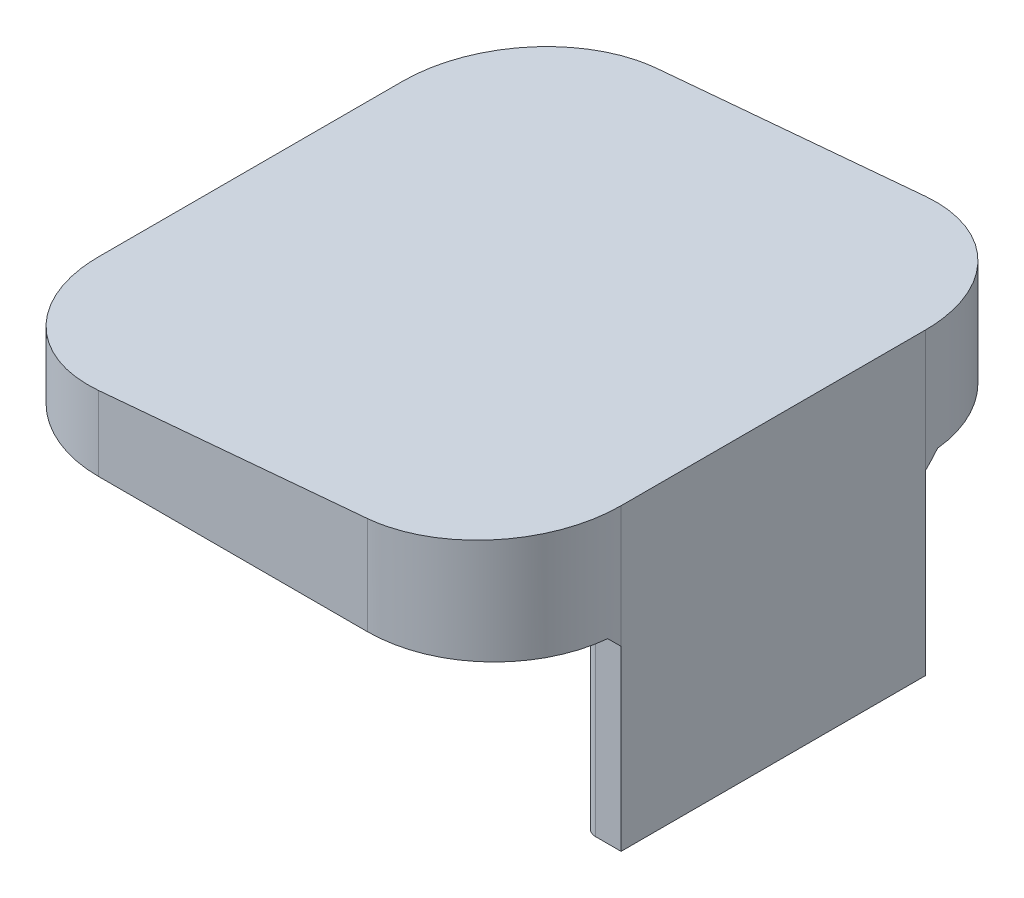
SolidWorks part; units mm, degrees
material "Custom Plastic"
ref_plane "Front Plane" through (0, 0, 0) normal (0, 0, 1) x (1, 0, 0)
ref_plane "Top Plane" through (0, 0, 0) normal (0, 1, 0) x (1, 0, 0)
ref_plane "Right Plane" through (0, 0, 0) normal (1, 0, 0) x (0, 0, -1)
sketch "Sketch1" plane through (0, 0, 0) normal (0, 0, 1) x (1, 0, 0)
  line L0 (-20.6, 0) -> (20.6, 0)
  line L1 (20.6, 0) -> (20.6, 8.6045)
  line L2 (20.6, 8.6045) -> (-20.6, 5)
  line L3 (-20.6, 5) -> (-20.6, 0)
  dimension "D1" = 41.2
  dimension "D2" = 5
  dimension "D3" = 85
extrude "Boss-Extrude1" add sketch "Sketch1" along normal blind 44
fillet "Fillet1" radius 10 4 edges at (-20.6, 2.5, 0) (-20.6, 2.5, 44) (20.6, 4.3023, 0) (20.6, 4.3023, 44)
sketch "Sketch5" plane through (0, 0, 0) normal (0, -1, 0) x (1, 0, 0)
  line L3 (17.6, 10) -> (17.6, 34)
  line L4 (-20.6, 34) -> (-20.6, 10)
  line L5 (-10.6, 0) -> (10.6, 0)
  line L6 (20.6, 10) -> (20.6, 34)
  line L7 (10.6, 44) -> (-10.6, 44)
  line L8 (-20.6, 34) -> (-20.6, 10)
  line L9 (-10.6, 0) -> (10.6, 0)
  line L10 (20.6, 10) -> (20.6, 34)
  line L15 (10.6, 41) -> (-10.6, 41) construction
  line L16 (-17.6, 34) -> (-17.6, 10) construction
  line L17 (-10.6, 3) -> (10.6, 3) construction
  line L18 (10.6, 44) -> (-10.6, 44) construction
  line L19 (17.6, 34) -> (20.6, 34)
  line L20 (17.6, 10) -> (20.6, 10)
  arc A4 (-20.6, 10) -> (-10.6, 0) centre (-10.6, 10) ccw
  arc A5 (10.6, 0) -> (20.6, 10) centre (10.6, 10) ccw
  arc A6 (20.6, 34) -> (10.6, 44) centre (10.6, 34) ccw
  arc A7 (-10.6, 44) -> (-20.6, 34) centre (-10.6, 34) ccw
  arc A8 (-20.6, 10) -> (-10.6, 0) centre (-10.6, 10) ccw
  arc A9 (10.6, 0) -> (20.6, 10) centre (10.6, 10) ccw
  arc A10 (20.6, 34) -> (10.6, 44) centre (10.6, 34) ccw
  arc A11 (-10.6, 44) -> (-20.6, 34) centre (-10.6, 34) ccw
  arc A12 (-10.6, 41) -> (-17.6, 34) centre (-10.6, 34) ccw construction
  arc A13 (-17.6, 10) -> (-10.6, 3) centre (-10.6, 10) ccw construction
  arc A18 (17.6, 34) -> (10.6, 41) centre (10.6, 34) ccw construction
  arc A19 (10.6, 3) -> (17.6, 10) centre (10.6, 10) ccw construction
  line M14 (20.6, 10) -> (20.6, 34)
  dimension "D2" = 3
  dimension "D1" = 0
extrude "Boss-Extrude3" add sketch "Sketch5" along normal blind 15 contours L3 L20 L19 M14 region at (19.1, 0, 22)
fillet "Fillet4" radius 1 2 edges at (17.6, -7.5, 34) (17.6, -7.5, 10)
chamfer "Chamfer3" distance 1 angle 45 5 edges at (19.6, 0, 34) (17.8929, 0, 33.7071) (17.6, 0, 22) (17.8929, 0, 10.2929) (19.6, 0, 10)
